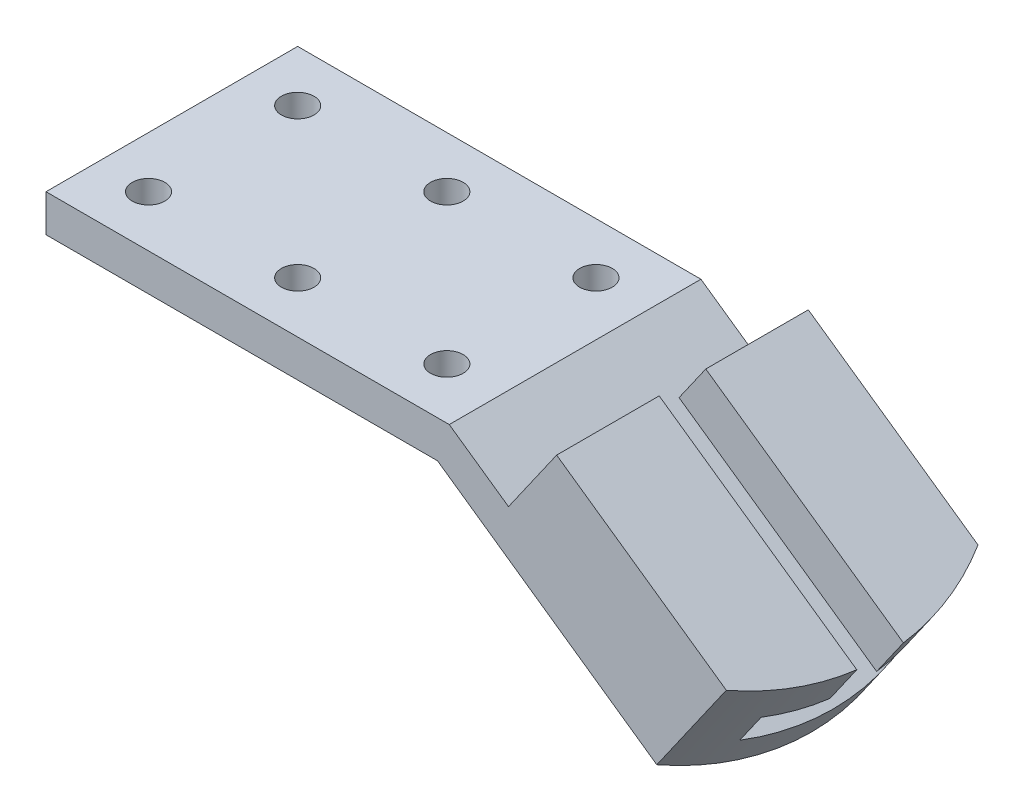
SolidWorks part; units mm, degrees
ref_plane "Front Plane" through (0, 0, 0) normal (0, 0, 1) x (1, 0, 0)
ref_plane "Top Plane" through (0, 0, 0) normal (0, 1, 0) x (1, 0, 0)
ref_plane "Right Plane" through (0, 0, 0) normal (1, 0, 0) x (0, 0, -1)
sketch "Sketch1" plane through (0, 0, 0) normal (0, 0, 1) x (1, 0, 0)
  line L0 (0, 0) -> (0, 8)
  line L1 (0, 8) -> (86.5224, 8)
  line L2 (86.5224, 8) -> (97.9476, 0)
  line L3 (97.9476, 0) -> (108.272, 14.7447)
  line L4 (108.272, 14.7447) -> (152.1579, -15.9845)
  line L6 (137.2449, -37.2825) -> (84, 0)
  line L7 (0, 0) -> (84, 0)
  line L8 (137.2449, -37.2825) -> (152.1579, -15.9845)
  point P8 (0, 0)
  dimension "D1" = 35
  dimension "D2" = 65
  dimension "D3" = 84
  dimension "D4" = 8
  dimension "D5" = 8
  dimension "D6" = 18
extrude "Boss-Extrude1" add sketch "Sketch1" along normal mid plane 54
sketch "Sketch2" plane through (0, 8, 0) normal (0, 1, 0) x (1, 0, 0)
  line L0 (86.5224, 27) -> (0, 27) construction
  line L1 (0, -27) -> (0, 27) construction
  circle A0 centre (11, 16) radius 3.5
  circle A1 centre (43, 16) radius 3.5
  circle A2 centre (75, 16) radius 3.5
  circle A3 centre (11, -16) radius 3.5
  circle A4 centre (43, -16) radius 3.5
  circle A5 centre (75, -16) radius 3.5
  dimension "D1" = 7
  dimension "D5" = 32
  dimension "D2" = 11
  dimension "D3" = 11
  dimension "D7" = 32
  dimension "D4" = 3
  dimension "D6" = 2
extrude "Cut-Extrude1" cut sketch "Sketch2" against normal up to surface (8 mm away) up to face at (42, 0, 0)
sketch "Sketch4" plane through (109.6097, -76.7496, 0) normal (0.8192, -0.5736, 0) x (0, 0, -1)
  line L0 (27, 48.1804) -> (27, 74.1804) construction
  line L1 (-27, 48.1804) -> (27, 48.1804)
  line L2 (-27, 48.1804) -> (-27, 56.1804)
  line L3 (-27, 56.1804) -> (27, 56.1804)
  line L4 (27, 48.1804) -> (27, 56.1804)
  line L6 (-27, 56.1804) -> (-27, 74.1804)
  line L7 (-27, 74.1804) -> (-5, 74.1804)
  line L8 (-27, 74.1804) -> (27, 74.1804) construction
  line L9 (-5, 74.1804) -> (-5, 64.1804)
  line L10 (-5, 64.1804) -> (-17.5, 64.1804)
  line L11 (-17.5, 64.1804) -> (-17.5, 56.1804)
  line L12 (0, 48.1804) -> (0, 74.1804) construction
  line L13 (17.5, 64.1804) -> (17.5, 56.1804)
  line L14 (5, 64.1804) -> (17.5, 64.1804)
  line L15 (5, 74.1804) -> (5, 64.1804)
  line L16 (27, 74.1804) -> (5, 74.1804)
  line L17 (27, 56.1804) -> (27, 74.1804)
  line M4 (27, 74.1804) -> (-27, 74.1804)
  dimension "D1" = 8
  dimension "D2" = 35
  dimension "D3" = 10
  dimension "D4" = 10
extrude "Cut-Extrude2" cut sketch "Sketch4" against normal up to surface (53.5748 mm away) contours L3 L12 L9 L10 L11 M4 | L12 L3 L13 L14 L15 M4 region at (145.4863, -25.5125, -7.1053) region at (145.4863, -25.5125, 7.1053) up to face at (103.1098, 7.3724, 0)
sketch "Sketch5" plane through (42.5481, 60.765, 0) normal (0.5736, 0.8192, 0) x (0.8192, -0.5736, 0)
  line L0 (133.8088, -27) -> (133.8088, -5) construction
  line L1 (133.8088, 5) -> (133.8088, 27) construction
  line L2 (133.8088, -27) -> (133.8088, -5)
  line L3 (133.8088, 5) -> (133.8088, 27)
  line L4 (133.8088, -17.5) -> (133.8088, 17.5) construction
  line L5 (133.8088, -17.5) -> (133.8088, 17.5)
  line L6 (0, 0) -> (81.8088, 0) construction
  line L7 (81.8088, -27) -> (81.8088, 27)
  line L8 (133.8088, 27) -> (80.234, 27) construction
  line L9 (81.8088, 27) -> (126.2497, 27)
  line L10 (81.8088, -27) -> (126.2497, -27)
  line L11 (81.8088, 27) -> (80.234, 27)
  line L12 (80.234, 27) -> (80.234, 5)
  line L13 (80.234, 5) -> (80.234, 27) construction
  line L14 (80.234, 5) -> (81.8088, 5)
  line L15 (81.8088, -27) -> (80.234, -27)
  line L16 (80.234, -27) -> (80.234, -5)
  line L17 (80.234, -5) -> (81.8088, -5)
  line L18 (80.234, 5) -> (133.8088, 5) construction
  line L19 (126.2497, 27) -> (133.8088, 27)
  line L20 (133.8088, -27) -> (126.2497, -27)
  arc A1 (126.2497, -27) -> (126.2497, 27) centre (81.8088, 0) ccw
  point P25 (81.0214, 5)
  line M1 (80.234, 27) -> (80.234, 5)
  line M2 (80.234, 5) -> (133.8088, 5)
  line M3 (133.8088, 5) -> (133.8088, 27)
  line M4 (133.8088, 27) -> (80.234, 27)
  dimension "D1" = 52
extrude "Cut-Extrude3" cut sketch "Sketch5" against normal up to surface (18 mm away) contours L7 M2 M4 M1 | L17 L16 L15 L7 region at (108.917, 14.2931, 16) region at (108.917, 14.2931, -16) up to face at (106.0628, -5.6823, 0)
extrude "Cut-Extrude4" cut sketch "Sketch5<4>" against normal up to surface (26 mm away) contours A1 L20 L2 L5 | A1 L3 M2 M3 M4 | A1 L5 M2 region at (150.326, -14.7018, 20.352) region at (152.0987, -15.9431, -3.7506) region at (150.3151, -14.6942, -20.4537) up to face at (110.6224, -18.6412, 0)
sketch "Sketch5<4>" plane through (42.5481, 60.765, 0) normal (0.5736, 0.8192, 0) x (0.8192, -0.5736, 0) same geometry as "Sketch5"
